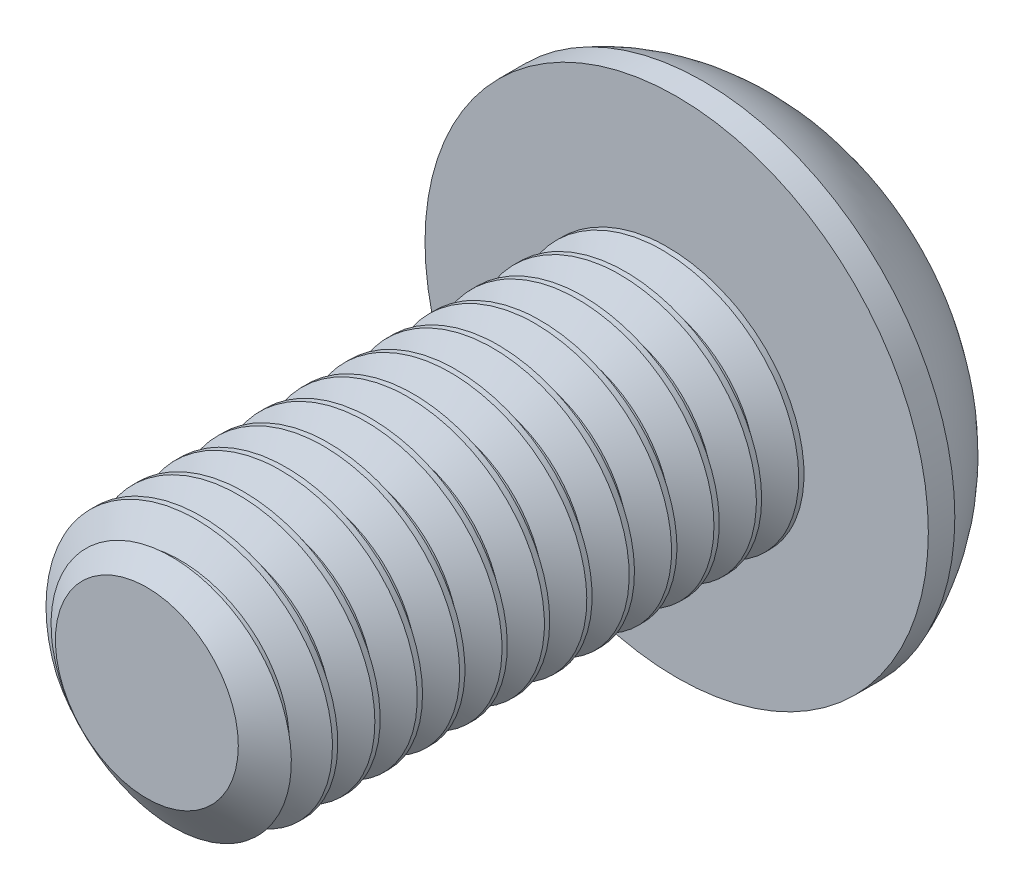
SolidWorks part; units mm, degrees
ref_plane "Front Plane" through (0, 0, 0) normal (0, 0, 1) x (1, 0, 0)
ref_plane "Top Plane" through (0, 0, 0) normal (0, 1, 0) x (1, 0, 0)
ref_plane "Right Plane" through (0, 0, 0) normal (1, 0, 0) x (0, 0, -1)
sketch "Sketch1" plane through (0, 0, 0) normal (0, 0, 1) x (1, 0, 0)
  circle A0 centre (0, 0) radius 2.5
  dimension "OD" = 5
extrude "Extrude1" add sketch "Sketch1" against normal blind 10
sketch "Sketch2" plane through (0, 0, 0) normal (0, 0, 1) x (1, 0, 0)
  circle A0 centre (0, 0) radius 2.5 construction
  circle A1 centre (0, 0) radius 2.5
curve "Helix/Spiral1" pitch 0.8 height 10.8 turns 13.5 parameters "pitch"=0.8
sketch "Sketch3" plane through (0, 0, 0) normal (1, 0, 0) x (0, 0, -1)
  line L0 (-0.7, 2.5) -> (-0.4, 1.9804)
  line L1 (-0.4, 1.9804) -> (-0.3, 1.9804)
  line L2 (-0.3, 1.9804) -> (0, 2.5)
  line L3 (-0.7, 2.5) -> (0, 2.5)
  line L4 (-0.35, 2.5) -> (-0.35, 1.9804) construction
  line L5 (-0.55, 2.2402) -> (-0.15, 2.2402) construction
  line L6 (0, 2.5) -> (0, -2.5) construction
  dimension "D1" = 0.1
  dimension "D2" = 0.4
  dimension "D3" = 60
sweep "Cut-Sweep1" cut profiles "Sketch3" path "Helix/Spiral1"
sketch "Sketch4" plane through (0, 0, 0) normal (1, 0, 0) x (0, 0, -1)
  line L0 (0.5417, 2.5) -> (0, 1.7264)
  line L1 (0, 1.7264) -> (0, 2.5)
  line L2 (0.5417, 2.5) -> (0, 2.5)
  line L3 (-0.7, 2.5) -> (0, 2.5) construction
  line L4 (0, 0) -> (7.0209, 0) construction
  dimension "D1" = 55
  dimension "D2" = 0.254
revolve "Cut-Revolve1" cut sketch "Sketch4" angle 360 about L4
sketch "Sketch5" plane through (0, 0, 0) normal (1, 0, 0) x (0, 0, -1)
  line L0 (10, -1.7838) -> (10, 1.991) construction
  line L1 (10, 2.627) -> (28.1202, 2.627)
  line L2 (10, 2.627) -> (10, 0)
  line L3 (10, 0) -> (28, 0)
  line L4 (28, 2.2968) -> (28, 0)
  line L5 (28.1202, 2.627) -> (28, 2.2968)
  line L6 (0, 0) -> (9.9695, 0) construction
  point P3 (28, 2.627)
  point P10 (28, 2.627)
  dimension "D1" = 0.3302
  dimension "Thread min" = 28
  dimension "D2" = 0.127
  dimension "D3" = 20
revolve "partially thread" [suppressed] add sketch "Sketch5" angle 360 about L6
sketch "Sketch6" plane through (0, 0, -10) normal (0, 0, -1) x (-1, 0, 0)
  circle A0 centre (0, 0) radius 4.75
  dimension "head dia" = 9.5
extrude "Extrude2" add sketch "Sketch6" along normal blind 2.75
sketch "Sketch10" plane through (0, 0, 0) normal (1, 0, 0) x (0, 0, -1)
  line L0 (12.75, -4.75) -> (12.75, 4.75) construction
  line L1 (0, 0) -> (15.9584, 0) construction
  line L2 (12.75, 4.75) -> (10, 4.75) construction
  line L3 (10, 4.75) -> (10, -4.75) construction
  line L4 (10.5, 4.75) -> (10.5, 5.25)
  line L5 (10.5, 5.25) -> (13.25, 5.25)
  line L6 (13.25, 5.25) -> (13.25, 1.5)
  line L7 (12.75, 1.5) -> (13.25, 1.5)
  arc A0 (12.75, 1.5) -> (10.5, 4.75) centre (9.2778, 1.5) ccw
  dimension "D1" = 3
  dimension "D2" = 0.5
  dimension "D3" = 0.5
revolve "Cut-Revolve2" cut sketch "Sketch10" angle 360 about L1
ref_plane "Plane1" through (0, 0, -12.75) normal (0, 0, 1) x (1, 0, 0)
sketch "Sketch7" plane through (0, 0, -12.75) normal (0, 0, -1) x (-1, 0, 0)
  line L1 (0, 1.7321) -> (-1.5, 0.866)
  line L2 (-1.5, 0.866) -> (-1.5, -0.866)
  line L3 (-1.5, -0.866) -> (0, -1.7321)
  line L4 (0, -1.7321) -> (1.5, -0.866)
  line L5 (1.5, -0.866) -> (1.5, 0.866)
  line L6 (1.5, 0.866) -> (0, 1.7321)
  circle A0 centre (0, 0) radius 1.5 construction
  dimension "hex dia" = 3
extrude "Cut-Extrude1" cut sketch "Sketch7" against normal blind 2.25
sketch "Sketch8" plane through (0, 0, -12.75) normal (0, 0, 1) x (1, 0, 0)
  circle A0 centre (0, 0) radius 1.7321
extrude "Cut-Extrude2" cut sketch "Sketch8" along normal through all draft 45
sketch "Sketch9" plane through (0, 0, 0) normal (1, 0, 0) x (0, 0, -1)
  line L0 (0, 2.5) -> (0, -2.5) construction
  line L1 (4.4, 2.5) -> (4.4, -2.5) construction
  dimension "D1" = 4.4
equation "\"D3@Helix/Spiral1\" = \"screw length@Extrude1\"+\"pitch@Helix/Spiral1\""
equation "\"D1@Sketch3\" = \"pitch@Helix/Spiral1\"*.125"
equation "\"D2@Sketch3\" = \"pitch@Helix/Spiral1\"*.5"
equation "\"D1@Cut-Extrude1\" = \"hex dia@Sketch7\"*.75"
equation "\"D1@Sketch9\" = \"pitch@Helix/Spiral1\"*5.5"
equation "\"D1@Sketch10\" = \"hex dia@Sketch7\""
equation "\"D1@Plane1\" = \"head depth@Extrude2\""
